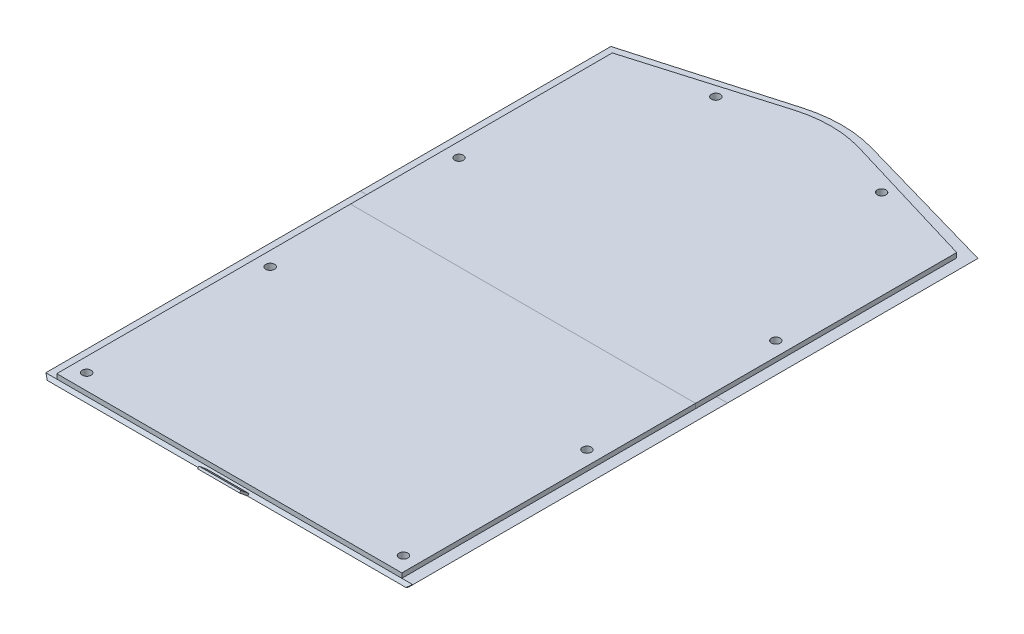
SolidWorks part; units mm, degrees
ref_plane "Front Plane" through (0, 0, 0) normal (0, 0, 1) x (1, 0, 0)
ref_plane "Top Plane" through (0, 0, 0) normal (0, 1, 0) x (1, 0, 0)
ref_plane "Right Plane" through (0, 0, 0) normal (1, 0, 0) x (0, 0, -1)
sketch "Sketch3" plane through (0, 0, 0) normal (0, -1, 0) x (1, 0, 0)
  line L0 (-82.5, -125) -> (-82.5, 140) construction
  line L1 (-15.1576, -144.8692) -> (-82.5, -125) construction
  line L2 (82.5923, -125) -> (15.2499, -144.8692) construction
  line L3 (82.5, 140) -> (82.5, -125) construction
  line L4 (-82.5, -125) -> (-82.5, 140) construction
  line L5 (-15.1576, -144.8692) -> (-82.5, -125) construction
  line L6 (82.5923, -125) -> (15.2499, -144.8692) construction
  line L7 (82.5, 140) -> (82.5, -125) construction
  line L8 (82.25, 140) -> (82.25, -124.5028)
  line L9 (82.5923, -125) -> (82.5, -125) construction
  line L10 (-15.0878, -144.6291) -> (-82.25, -124.8131)
  line L11 (-82.25, -124.8131) -> (-82.25, 140)
  line L12 (82.25, -124.5028) -> (15.1801, -144.6291)
  line L13 (82.25, 140) -> (-82.25, 140)
  line L14 (82.5216, -124.7602) -> (15.1801, -144.6291) construction
  line L15 (82.25, 140) -> (82.25, -125) construction
  arc A0 (-15.1576, -144.8692) -> (0.0462, -146.9988) centre (-0.0004, -91.995) ccw construction
  arc A1 (0.0462, -146.9988) -> (15.2499, -144.8692) centre (0.0928, -91.995) ccw construction
  arc A2 (-15.1576, -144.8692) -> (0.0462, -146.9988) centre (-0.0004, -91.995) ccw construction
  arc A3 (0.0462, -146.9988) -> (15.2499, -144.8692) centre (0.0928, -91.995) ccw construction
  arc A4 (0.0462, -146.7488) -> (15.1801, -144.6291) centre (0.0928, -91.995) ccw
  arc A5 (-15.0878, -144.6291) -> (0.0462, -146.7488) centre (-0.0004, -91.995) ccw
  dimension "D1" = 0.25
extrude "Boss-Extrude1" add sketch "Sketch3" against normal blind 2.25
sketch "Sketch4" plane through (0, 0, 0) normal (0, -1, 0) x (1, 0, 0)
  line L0 (87.5, 140) -> (-87.5, 140)
  line L11 (82.5, -125) -> (82.5923, -125)
  line L12 (82.5923, -125) -> (15.2499, -144.8692)
  line L13 (-15.1576, -144.8692) -> (-82.5, -125)
  line L14 (-82.5, -125) -> (-82.5, 140)
  line L15 (-82.5, 140) -> (-87.5, 140)
  line L16 (-87.5, 140) -> (-87.5, -129.3998)
  line L17 (-87.5, -129.3998) -> (-16.4833, -149.6903)
  line L18 (16.4833, -149.6903) -> (87.5, -129.3998)
  line L19 (87.5, -129.3998) -> (87.5, 140)
  line L20 (87.5, 140) -> (82.5, 140)
  line L21 (82.5, 140) -> (82.5, -125)
  line L27 (-87.5, 140) -> (-87.5, -129.3998)
  line L28 (-87.5, -129.3998) -> (-16.4833, -149.6903)
  line L29 (16.4833, -149.6903) -> (87.5, -129.3998)
  line L30 (87.5, -129.3998) -> (87.5, 140)
  arc A3 (0.0462, -146.9988) -> (15.2499, -144.8692) centre (0.0928, -91.995) ccw
  arc A4 (-15.1576, -144.8692) -> (0.0462, -146.9988) centre (-0.0004, -91.995) ccw
  arc A5 (-16.4833, -149.6903) -> (16.4833, -149.6903) centre (0, -91.9988) ccw
  arc A8 (-16.4833, -149.6903) -> (16.4833, -149.6903) centre (0, -91.9988) ccw
  dimension "D1" = 0
extrude "Boss-Extrude2" add sketch "Sketch4" along normal blind 2
chamfer "Chamfer1" distance 2 angle 45 5 edges at (87.5, -2, 5.3001) (51.9916, -2, -139.545) (0, -2, -151.9988) (-51.9916, -2, -139.545) (-87.5, -2, 5.3001)
sketch "Sketch5" plane through (0, -2, 0) normal (0, -1, 0) x (1, 0, 0)
  line L0 (-76.1767, 137.5155) -> (-80.1767, 135.2061) construction
  line L1 (-80.1767, 135.2061) -> (-80.1767, 130.5873) construction
  line L2 (-80.1767, 130.5873) -> (-76.1767, 128.2779) construction
  line L3 (-76.1767, 128.2779) -> (-72.1767, 130.5873) construction
  line L4 (-72.1767, 130.5873) -> (-72.1767, 135.2061) construction
  line L5 (-72.1767, 135.2061) -> (-76.1767, 137.5155) construction
  line L6 (75.5, 137.1) -> (71.5, 134.7906) construction
  line L7 (71.5, 134.7906) -> (71.5, 130.1718) construction
  line L8 (71.5, 130.1718) -> (75.5, 127.8624) construction
  line L9 (75.5, 127.8624) -> (79.5, 130.1718) construction
  line L10 (79.5, 130.1718) -> (79.5, 134.7906) construction
  line L11 (79.5, 134.7906) -> (75.5, 137.1) construction
  line L12 (75.5, 40.4) -> (79.5, 42.7094) construction
  line L13 (79.5, 42.7094) -> (79.5, 47.3282) construction
  line L14 (79.5, 47.3282) -> (75.5, 49.6376) construction
  line L15 (75.5, 49.6376) -> (71.5, 47.3282) construction
  line L16 (71.5, 47.3282) -> (71.5, 42.7094) construction
  line L17 (71.5, 42.7094) -> (75.5, 40.4) construction
  line L18 (75.5, -40.4) -> (71.5, -42.7094) construction
  line L19 (71.5, -42.7094) -> (71.5, -47.3282) construction
  line L20 (71.5, -47.3282) -> (75.5, -49.6376) construction
  line L21 (75.5, -49.6376) -> (79.5, -47.3282) construction
  line L22 (79.5, -47.3282) -> (79.5, -42.7094) construction
  line L23 (79.5, -42.7094) -> (75.5, -40.4) construction
  line L24 (-39.5, -126.8131) -> (-43.5, -129.1225) construction
  line L25 (-43.5, -129.1225) -> (-43.5, -133.7413) construction
  line L26 (-43.5, -133.7413) -> (-39.5, -136.0507) construction
  line L27 (-39.5, -136.0507) -> (-35.5, -133.7413) construction
  line L28 (-35.5, -133.7413) -> (-35.5, -129.1225) construction
  line L29 (-35.5, -129.1225) -> (-39.5, -126.8131) construction
  line L30 (39.5, -126.8131) -> (35.5, -129.1225) construction
  line L31 (35.5, -129.1225) -> (35.5, -133.7413) construction
  line L32 (35.5, -133.7413) -> (39.5, -136.0507) construction
  line L33 (39.5, -136.0507) -> (43.5, -133.7413) construction
  line L34 (43.5, -133.7413) -> (43.5, -129.1225) construction
  line L35 (43.5, -129.1225) -> (39.5, -126.8131) construction
  line L36 (-75.5, 40.4) -> (-71.5, 42.7094) construction
  line L37 (-71.5, 42.7094) -> (-71.5, 47.3282) construction
  line L38 (-71.5, 47.3282) -> (-75.5, 49.6376) construction
  line L39 (-75.5, 49.6376) -> (-79.5, 47.3282) construction
  line L40 (-79.5, 47.3282) -> (-79.5, 42.7094) construction
  line L41 (-79.5, 42.7094) -> (-75.5, 40.4) construction
  line L42 (-75.5, -40.4) -> (-79.5, -42.7094) construction
  line L43 (-79.5, -42.7094) -> (-79.5, -47.3282) construction
  line L44 (-79.5, -47.3282) -> (-75.5, -49.6376) construction
  line L45 (-75.5, -49.6376) -> (-71.5, -47.3282) construction
  line L46 (-71.5, -47.3282) -> (-71.5, -42.7094) construction
  line L47 (-71.5, -42.7094) -> (-75.5, -40.4) construction
  line L48 (-76.1767, 137.5155) -> (-80.1767, 135.2061) construction
  line L49 (-80.1767, 135.2061) -> (-80.1767, 130.5873) construction
  line L50 (-80.1767, 130.5873) -> (-76.1767, 128.2779) construction
  line L51 (-76.1767, 128.2779) -> (-72.1767, 130.5873) construction
  line L52 (-72.1767, 130.5873) -> (-72.1767, 135.2061) construction
  line L53 (-72.1767, 135.2061) -> (-76.1767, 137.5155) construction
  line L54 (75.5, 137.1) -> (71.5, 134.7906) construction
  line L55 (71.5, 134.7906) -> (71.5, 130.1718) construction
  line L56 (71.5, 130.1718) -> (75.5, 127.8624) construction
  line L57 (75.5, 127.8624) -> (79.5, 130.1718) construction
  line L58 (79.5, 130.1718) -> (79.5, 134.7906) construction
  line L59 (79.5, 134.7906) -> (75.5, 137.1) construction
  line L60 (75.5, 40.4) -> (79.5, 42.7094) construction
  line L61 (79.5, 42.7094) -> (79.5, 47.3282) construction
  line L62 (79.5, 47.3282) -> (75.5, 49.6376) construction
  line L63 (75.5, 49.6376) -> (71.5, 47.3282) construction
  line L64 (71.5, 47.3282) -> (71.5, 42.7094) construction
  line L65 (71.5, 42.7094) -> (75.5, 40.4) construction
  line L66 (75.5, -40.4) -> (71.5, -42.7094) construction
  line L67 (71.5, -42.7094) -> (71.5, -47.3282) construction
  line L68 (71.5, -47.3282) -> (75.5, -49.6376) construction
  line L69 (75.5, -49.6376) -> (79.5, -47.3282) construction
  line L70 (79.5, -47.3282) -> (79.5, -42.7094) construction
  line L71 (79.5, -42.7094) -> (75.5, -40.4) construction
  line L72 (-39.5, -126.8131) -> (-43.5, -129.1225) construction
  line L73 (-43.5, -129.1225) -> (-43.5, -133.7413) construction
  line L74 (-43.5, -133.7413) -> (-39.5, -136.0507) construction
  line L75 (-39.5, -136.0507) -> (-35.5, -133.7413) construction
  line L76 (-35.5, -133.7413) -> (-35.5, -129.1225) construction
  line L77 (-35.5, -129.1225) -> (-39.5, -126.8131) construction
  line L78 (39.5, -126.8131) -> (35.5, -129.1225) construction
  line L79 (35.5, -129.1225) -> (35.5, -133.7413) construction
  line L80 (35.5, -133.7413) -> (39.5, -136.0507) construction
  line L81 (39.5, -136.0507) -> (43.5, -133.7413) construction
  line L82 (43.5, -133.7413) -> (43.5, -129.1225) construction
  line L83 (43.5, -129.1225) -> (39.5, -126.8131) construction
  line L84 (-75.5, 40.4) -> (-71.5, 42.7094) construction
  line L85 (-71.5, 42.7094) -> (-71.5, 47.3282) construction
  line L86 (-71.5, 47.3282) -> (-75.5, 49.6376) construction
  line L87 (-75.5, 49.6376) -> (-79.5, 47.3282) construction
  line L88 (-79.5, 47.3282) -> (-79.5, 42.7094) construction
  line L89 (-79.5, 42.7094) -> (-75.5, 40.4) construction
  line L90 (-75.5, -40.4) -> (-79.5, -42.7094) construction
  line L91 (-79.5, -42.7094) -> (-79.5, -47.3282) construction
  line L92 (-79.5, -47.3282) -> (-75.5, -49.6376) construction
  line L93 (-75.5, -49.6376) -> (-71.5, -47.3282) construction
  line L94 (-71.5, -47.3282) -> (-71.5, -42.7094) construction
  line L95 (-71.5, -42.7094) -> (-75.5, -40.4) construction
  line L96 (0, -33) -> (0, 33) construction
  circle A0 centre (39.5, -131.4319) radius 2.1
  circle A1 centre (75.5, -45.0188) radius 2.1
  circle A2 centre (75.5, 45.0188) radius 2.1
  circle A3 centre (75.5, 132.4812) radius 2.1
  circle A4 centre (-75.5, 132.4812) radius 2.1
  circle A5 centre (-75.5, 45.0188) radius 2.1
  circle A6 centre (-75.5, -45.0188) radius 2.1
  circle A7 centre (-39.5, -131.4319) radius 2.1
  point P6 (71.5, -45.0188)
  point P8 (35.5, -131.4319)
  point P14 (71.5, 45.0188)
  point P23 (0, 0)
  point P26 (71.5, 132.4812)
  dimension "D1" = 4.2
extrude "Cut-Extrude1" cut sketch "Sketch5" against normal up to next
sketch "Sketch6" plane through (0, 0, 0) normal (1, 0, 0) x (0, 0, -1)
  line L0 (10, -2) -> (10, 0)
  line L1 (127.8912, -2) -> (-140, -2) construction
  line L2 (10, 0) -> (0, 0)
  line L3 (0, 0) -> (0, 2.25)
  line L4 (124.5028, 2.25) -> (-140, 2.25) construction
  line L5 (129.3998, 0) -> (-140, 0) construction
  dimension "D1" = 10
split "Split1" trim tools "Sketch6" bodies to split 103 resulting bodies 104 105
sketch "Sketch7" plane through (0, 0, 0) normal (0, -1, 0) x (1, 0, 0)
  line L0 (82.25, -10) -> (82.25, 0) construction
  line L1 (0, -2.3375) -> (0, 2.3375) construction
  circle A0 centre (72.25, -5) radius 2.25
  circle A1 centre (-72.25, -5) radius 2.25
  point P4 (0, 0)
  point P5 (82.25, -5)
  dimension "D1" = 4.5
  dimension "D2" = 10
extrude "Boss-Extrude3" add sketch "Sketch7" along normal blind 2
chamfer "Chamfer2" distance 0.25 angle 45 2 edges at (72.25, -2, -7.25) (-72.25, -2, -2.75)
sketch "Sketch9" plane through (0, 0, 0) normal (0, 1, 0) x (1, 0, 0)
  line L1 (72.25, 0) -> (72.25, 10) construction
  line L2 (-87.5, 10) -> (87.5, 10) construction
  line L3 (-82.25, 0) -> (82.25, 0) construction
  line L4 (0, -2.3375) -> (0, 2.3375) construction
  line L5 (82.25, 124.5028) -> (82.25, 0) construction
  circle A0 centre (72.25, 5) radius 2.5
  circle A1 centre (-72.25, 5) radius 2.5
  point P4 (0, 0)
  point P10 (72.25, 5)
  point P12 (0, 0)
  point P13 (0, 0)
  dimension "D1" = 5
  dimension "D2" = 10
extrude "Cut-Extrude2" cut sketch "Sketch9" against normal blind 2
other "Save Bodies1"
sketch "Sketch12" plane through (0, 0, 0) normal (1, 0, 0) x (0, 0, -1)
  line L0 (-140, -2) -> (-140, 0)
  line L1 (-140, 0) -> (-141.2804, -1.5364)
  line L2 (-141.2804, -1.5364) -> (-140, -2)
  point P3 (0, 0)
  point P5 (0, 0)
  point P7 (-141.2804, -1.5364)
extrude "Boss-Extrude5" add sketch "Sketch12" along normal up to vertex (87.5 mm away) and the other way up to vertex (87.5 mm away) up to point (87.5, 0, -10) other way up to point (-87.5, 0, -10)
chamfer "Chamfer3" distance 2 angle 45 2 edges at (87.5, -1.7682, 140.6402) (-87.5, -1.7682, 140.6402)
sketch "Sketch13" plane through (0, 68.8525, 82.623) normal (0, 0.6402, 0.7682) x (1, 0, 0)
  line L0 (85.5, -91.6258) -> (-85.5, -91.6258) construction
  line L1 (10, -91.6258) -> (-10, -91.6258)
  line L2 (10, -91.6258) -> (10, -90.6258)
  line L3 (10, -90.6258) -> (-10, -90.6258)
  line L4 (-10, -91.6258) -> (-10, -90.6258)
  point P6 (0, -91.6258)
  point P7 (0, -91.6258)
  dimension "D1" = 20
  dimension "D2" = 1
extrude "Boss-Extrude6" add sketch "Sketch13" along normal blind 5
